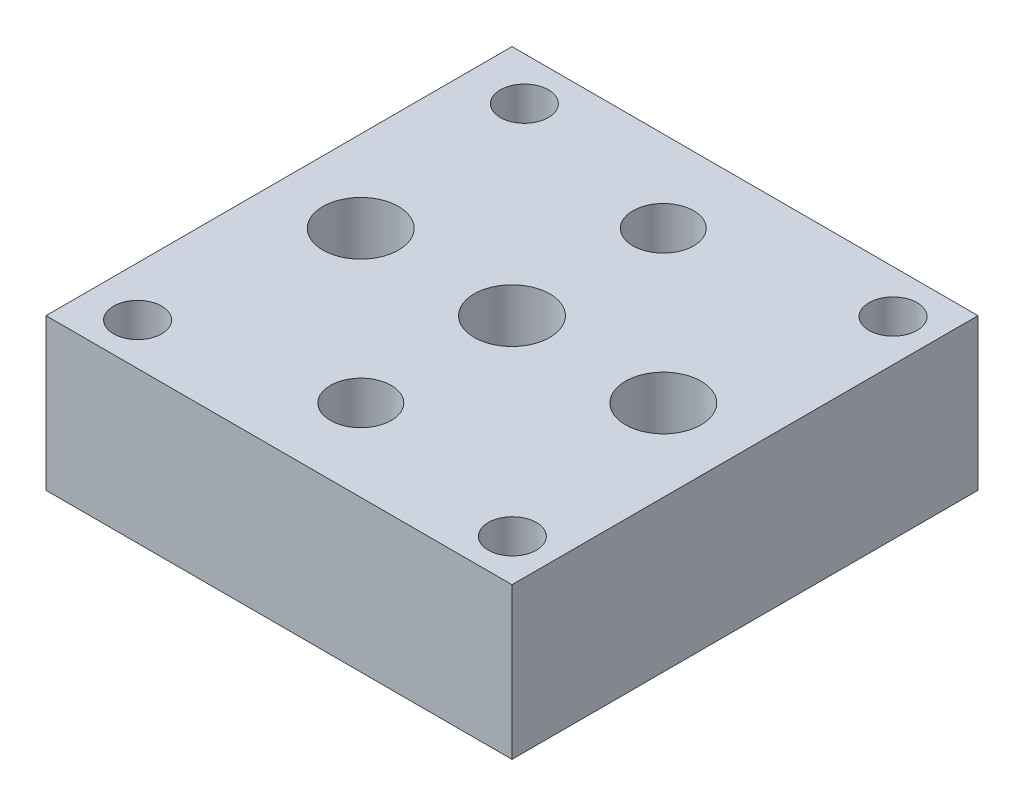
SolidWorks part; units mm, degrees
ref_plane "Front Plane" through (0, 0, 0) normal (0, 0, 1) x (1, 0, 0)
ref_plane "Top Plane" through (0, 0, 0) normal (0, 1, 0) x (1, 0, 0)
ref_plane "Right Plane" through (0, 0, 0) normal (1, 0, 0) x (0, 0, -1)
sketch "Sketch1" plane through (0, 0, 0) normal (0, 1, 0) x (1, 0, 0)
  line L1 (-19.558, 19.558) -> (19.558, 19.558)
  line L2 (-19.558, 19.558) -> (-19.558, -19.558)
  line L3 (-19.558, -19.558) -> (19.558, -19.558)
  line L4 (19.558, 19.558) -> (19.558, -19.558)
  line L5 (-19.558, 19.558) -> (19.558, -19.558) construction
  line L6 (-19.558, -19.558) -> (19.558, 19.558) construction
  point P0 (0, 0)
extrude "Boss-Extrude1" add sketch "Sketch1" along normal blind 12.7
sketch "Sketch2" plane through (0, 12.7, 0) normal (0, 1, 0) x (1, 0, 0)
  line L0 (19.558, 19.558) -> (16.058, 19.558)
  line L1 (19.558, 19.558) -> (-19.558, 19.558) construction
  line L2 (16.058, 19.558) -> (16.058, 15.928)
  line L3 (-19.558, -19.558) -> (-15.398, -19.558)
  line L4 (-19.558, -19.558) -> (19.558, -19.558) construction
  line L5 (-15.398, -19.558) -> (-15.398, -16.028)
  line L6 (19.558, -19.558) -> (16.058, -19.558)
  line L7 (16.058, -19.558) -> (16.058, -16.028)
  point P0 (0, 0)
ref_axis "Axis1" through (0, 12.7, 0) along (0, 1, 0)
sketch "Sketch3" plane through (0, 12.7, 0) normal (0, 1, 0) x (1, 0, 0)
  line L0 (-19.558, 19.558) -> (-14.89, 19.558)
  line L1 (19.558, 19.558) -> (-19.558, 19.558) construction
  line L2 (-14.89, 19.558) -> (-14.89, 15.928)
hole_wizard "#21 (0.159) Diameter Hole1" positions "Sketch6" profile "Sketch5" hole size "#21" standard "ANSI Inch" end condition up to next
sketch "Sketch6" plane through (0, 12.7, 0) normal (0, 1, 0) x (1, 0, 0)
  point P0 (-14.89, 15.928)
  point P4 (-15.398, -16.028)
  point P7 (16.058, -16.028)
  point P10 (16.058, 15.928)
sketch "Sketch5" plane through (-14.89, 12.7, -15.928) normal (1, 0, 0) x (0, 0, 1)
  line L0 (0, 0) -> (0, 12.7)
  line L1 (0, 12.7) -> (2.0193, 12.7)
  line L2 (2.0193, 12.7) -> (2.0193, 0)
  line L5 (2.0193, 0) -> (0, 0)
  line L11 (0, -6.35) -> (0, 107.95) construction
  dimension "Thru Hole Dia." = 4.0386
  dimension "Thru Hole Depth" = 12.7
hole_wizard "1/4 (0.25) Diameter Hole1" positions "Sketch7" profile "Sketch8" hole size "1/4" standard "ANSI Inch" end condition up to next
sketch "Sketch7" plane through (0, 12.7, 0) normal (0, 1, 0) x (1, 0, 0)
  point P0 (0, 0)
sketch "Sketch8" plane through (0, 12.7, 0) normal (1, 0, 0) x (0, 0, 1)
  line L0 (0, 0) -> (0, 12.7)
  line L1 (0, 12.7) -> (3.175, 12.7)
  line L2 (3.175, 12.7) -> (3.175, 0)
  line L5 (3.175, 0) -> (0, 0)
  line L11 (0, -6.35) -> (0, 107.95) construction
  dimension "Thru Hole Dia." = 6.35
  dimension "Thru Hole Depth" = 12.7
sketch "Sketch9" plane through (0, 12.7, 0) normal (0, 1, 0) x (1, 0, 0)
  line L0 (0, 0) -> (19.558, 0)
  line L1 (19.558, -19.558) -> (19.558, 19.558) construction
  line L2 (0, 0) -> (-19.558, 0)
  line L3 (-19.558, 19.558) -> (-19.558, -19.558) construction
pattern_linear "LPattern1" count 2 spacing 12.7 along (-1, 0, 0) count 2 spacing 12.7 along (1, 0, 0) of "1/4 (0.25) Diameter Hole1"
sketch "Sketch10" plane through (0, 12.7, 0) normal (0, 1, 0) x (1, 0, 0)
  line L0 (0, 0) -> (0, 12.7)
  line L3 (0, 0) -> (0, -12.6907)
hole_wizard "1/4-20 Tapped Hole1" positions "Sketch13" profile "Sketch14" tap size "1/4-20" standard "ANSI Inch" end condition up to next
sketch "Sketch13" plane through (0, 12.7, 0) normal (0, 1, 0) x (1, 0, 0)
  point P0 (0, 12.7)
  point P3 (0, -12.6907)
sketch "Sketch14" plane through (0, 12.7, -12.7) normal (1, 0, 0) x (0, 0, 1)
  line L0 (0, 0) -> (0, 12.7)
  line L1 (0, 12.7) -> (2.5527, 12.7)
  line L2 (2.5527, 12.7) -> (2.5527, 0)
  line L5 (2.5527, 0) -> (0, 0)
  line L11 (0, -6.35) -> (0, 107.95) construction
  dimension "Thru Tap Drill Dia." = 5.1054
  dimension "Thru Tap Drill Depth" = 12.7
cosmetic thread "Hole Thread1" parameters "D2"=6.35
cosmetic thread "Hole Thread2" parameters "D2"=6.35
